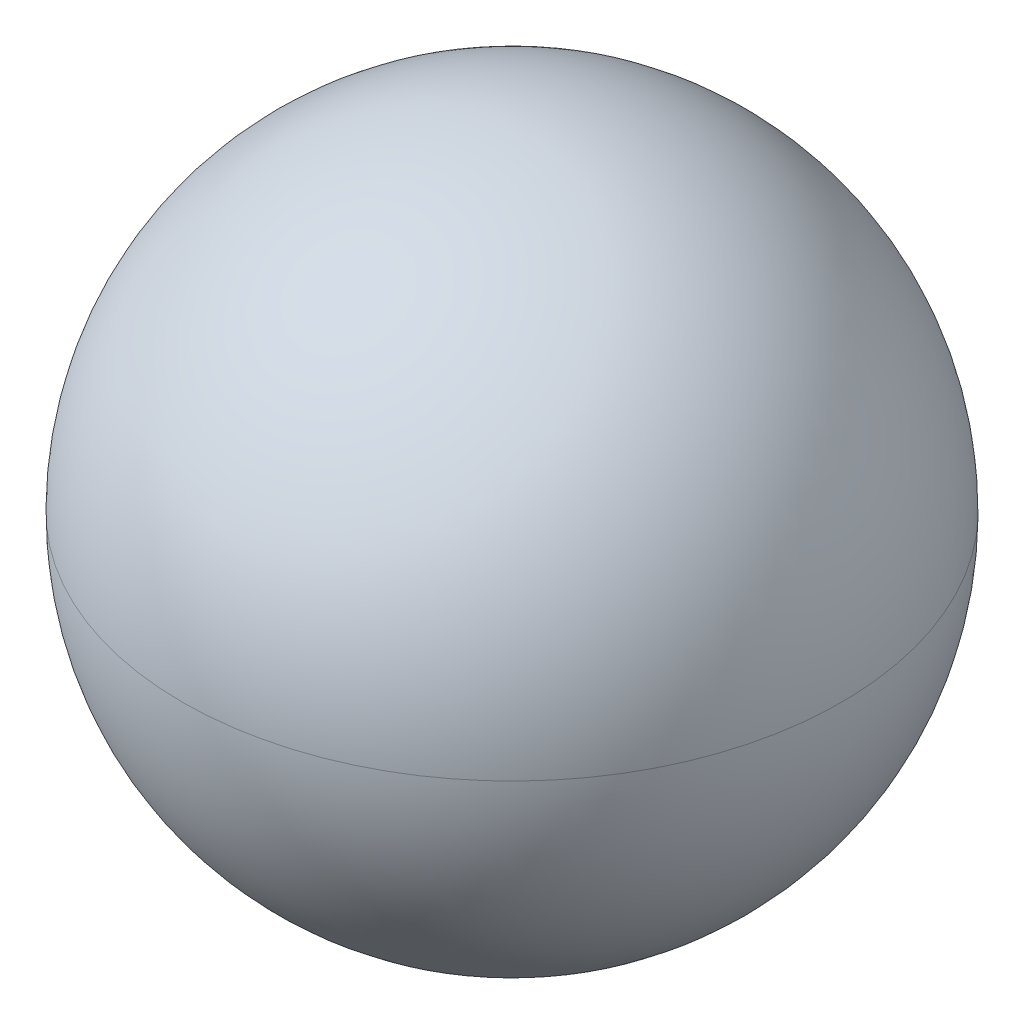
SolidWorks part; units mm, degrees
ref_plane "Front Plane" through (0, 0, 0) normal (0, 0, 1) x (1, 0, 0)
ref_plane "Top Plane" through (0, 0, 0) normal (0, 1, 0) x (1, 0, 0)
ref_plane "Right Plane" through (0, 0, 0) normal (1, 0, 0) x (0, 0, -1)
sketch "Sketch1" plane through (0, 0, 0) normal (0, 1, 0) x (1, 0, 0)
  circle A0 centre (0, 0) radius 25.4
  dimension "D1" = 50.8
extrude "Boss-Extrude1" add sketch "Sketch1" along normal blind 50.8
fillet "Fillet1" radius 25.4 2 edges at (0, 0, 25.4) (0, 50.8, 25.4)
